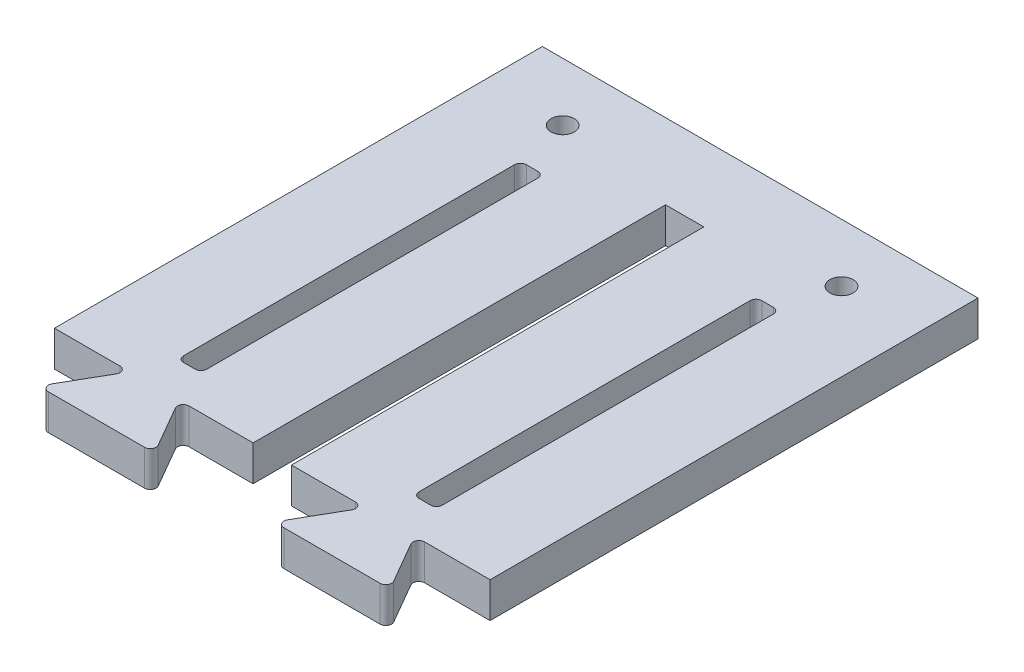
SolidWorks part; units mm, degrees
ref_plane "Front Plane" through (0, 0, 0) normal (0, 0, 1) x (1, 0, 0)
ref_plane "Top Plane" through (0, 0, 0) normal (0, 1, 0) x (1, 0, 0)
ref_plane "Right Plane" through (0, 0, 0) normal (1, 0, 0) x (0, 0, -1)
sketch "Sketch1" plane through (0, 0, 0) normal (0, 1, 0) x (1, 0, 0)
  line L0 (-19.25, 0) -> (-19.25, 42)
  line L1 (-19.25, 42) -> (19.25, 42)
  line L2 (19.25, 42) -> (19.25, 0)
  line L3 (19.25, 0) -> (12.25, 0)
  line L4 (12.25, 0) -> (15.1368, -5)
  line L5 (15.1368, -5) -> (5.1368, -5)
  line L6 (5.1368, -5) -> (8.0235, 0)
  line L7 (8.0235, 0) -> (-8.0235, 0)
  line L8 (-8.0235, 0) -> (-5.1368, -5)
  line L9 (-5.1368, -5) -> (-15.1368, -5)
  line L10 (-15.1368, -5) -> (-12.25, 0)
  line L11 (-12.25, 0) -> (-19.25, 0)
  point P13 (0, 0)
  dimension "D1" = 42
  dimension "D2" = 38.5
  dimension "D3" = 10
  dimension "D4" = 10
  dimension "D5" = 60
  dimension "D6" = 60
  dimension "D7" = 7
  dimension "D8" = 7
  dimension "D9" = 5
  dimension "D10" = 5
extrude "Boss-Extrude1" add sketch "Sketch1" along normal blind 3.05
fillet "Fillet1" radius 0.5 8 edges at (12.25, 1.525, 0) (15.1368, 1.525, 5) (5.1368, 1.525, 5) (8.0235, 1.525, 0) (-8.0235, 1.525, 0) (-5.1368, 1.525, 5) (-15.1368, 1.525, 5) (-12.25, 1.525, 0)
sketch "Sketch3" plane through (0, 3.05, 0) normal (0, 1, 0) x (1, 0, 0)
  line L0 (0, 40) -> (0, 0) construction
  line L2 (19.25, 42) -> (-19.25, 42) construction
  line L3 (-1.65, 35.5) -> (1.65, 35.5)
  line L4 (-1.65, 35.5) -> (-1.65, -4.5)
  line L5 (-1.65, -4.5) -> (1.65, -4.5)
  line L6 (1.65, 35.5) -> (1.65, -4.5)
  line L8 (-1.65, -5.7) -> (1.65, -5.7)
  line L9 (-1.65, -5.7) -> (-1.65, -6.7)
  line L10 (-1.65, -6.7) -> (1.65, -6.7)
  line L11 (1.65, -5.7) -> (1.65, -6.7)
  point P8 (0, 35.5)
  point P15 (0, -5.7)
  dimension "D1" = 3.3
  dimension "D2" = 40
  dimension "D3" = 6.5
  dimension "D4" = 1.2
  dimension "D5" = 1
extrude "Cut-Extrude2" cut sketch "Sketch3" against normal through all
sketch "Sketch8" plane through (0, 3.05, 0) normal (0, 1, 0) x (1, 0, 0)
  line L0 (0, 0) -> (0, 40) construction
  line L1 (-11.1368, 32.5) -> (-9.1368, 32.5)
  line L2 (-11.1368, 32.5) -> (-11.1368, 3)
  line L3 (-11.1368, 3) -> (-9.1368, 3)
  line L4 (-9.1368, 32.5) -> (-9.1368, 3)
  line L5 (-19.25, 0) -> (-13.116, 0) construction
  line L6 (-14.2707, -5) -> (-6.0028, -5) construction
  line L8 (11.1368, 3) -> (9.1368, 3)
  line L9 (9.1368, 32.5) -> (9.1368, 3)
  line L10 (11.1368, 32.5) -> (9.1368, 32.5)
  line L11 (11.1368, 32.5) -> (11.1368, 3)
  line L12 (1.65, 35.5) -> (-1.65, 35.5) construction
  point P5 (-10.1368, -5)
  point P10 (-10.1368, 3)
  dimension "D1" = 2
  dimension "D2" = 3
  dimension "D3" = 3
extrude "Cut-Extrude3" cut sketch "Sketch8" against normal through all
fillet "Fillet2" radius 0.5 8 edges at (11.1368, 1.525, -3) (9.1368, 1.525, -3) (11.1368, 1.525, -32.5) (9.1368, 1.525, -32.5) (-9.1368, 1.525, -3) (-9.1368, 1.525, -32.5) (-11.1368, 1.525, -32.5) (-11.1368, 1.525, -3)
sketch "Damper Hole Locations" plane through (0, 3.05, 0) normal (0, 1, 0) x (1, 0, 0)
  line L0 (0, 40) -> (0, 0) construction
  line L3 (19.25, 42) -> (-19.25, 42) construction
  circle A0 centre (-12, 37) radius 1.5
  circle A1 centre (12, 37) radius 1.5
  dimension "D1" = 3
  dimension "D2" = 12
  dimension "D3" = 5
hole_wizard "M3 Tapped Damper Holes" positions "Sketch6" profile "Sketch7" hole size "Ø2.0" standard "ANSI Metric" end condition through all
sketch "Sketch6" plane through (0, 3.05, 0) normal (0, 1, 0) x (1, 0, 0)
  point P0 (-12, 37)
  point P3 (12, 37)
sketch "Sketch7" plane through (-12, 3.05, -37) normal (1, 0, 0) x (0, 0, 1)
  line L0 (0, 0) -> (0, 3.05)
  line L1 (0, 3.05) -> (1, 3.05)
  line L2 (1, 3.05) -> (1, 0)
  line L5 (1, 0) -> (0, 0)
  line L11 (0, -6.35) -> (0, 107.95) construction
  dimension "Thru Hole Dia." = 2
  dimension "Thru Hole Depth" = 3.05
sketch "Sketch9" plane through (0, 3.05, 0) normal (0, 1, 0) x (1, 0, 0)
  line L0 (-19.25, 42) -> (-18.75, 42)
  line L1 (19.25, 42) -> (-19.25, 42) construction
  line L2 (-18.75, 42) -> (-18.75, 0)
  line L3 (-19.25, 0) -> (-13.116, 0) construction
  line L4 (-18.75, 0) -> (-19.25, 0)
  line L5 (-19.25, 0) -> (-19.25, 42)
  line L6 (19.25, 42) -> (18.75, 42)
  line L7 (18.75, 42) -> (18.75, 0)
  line L8 (13.116, 0) -> (19.25, 0) construction
  line L9 (18.75, 0) -> (19.25, 0)
  line L10 (19.25, 0) -> (19.25, 42)
  dimension "D1" = 0.5
  dimension "D2" = 0.5
extrude "Cut-Extrude4" cut sketch "Sketch9" against normal through all
